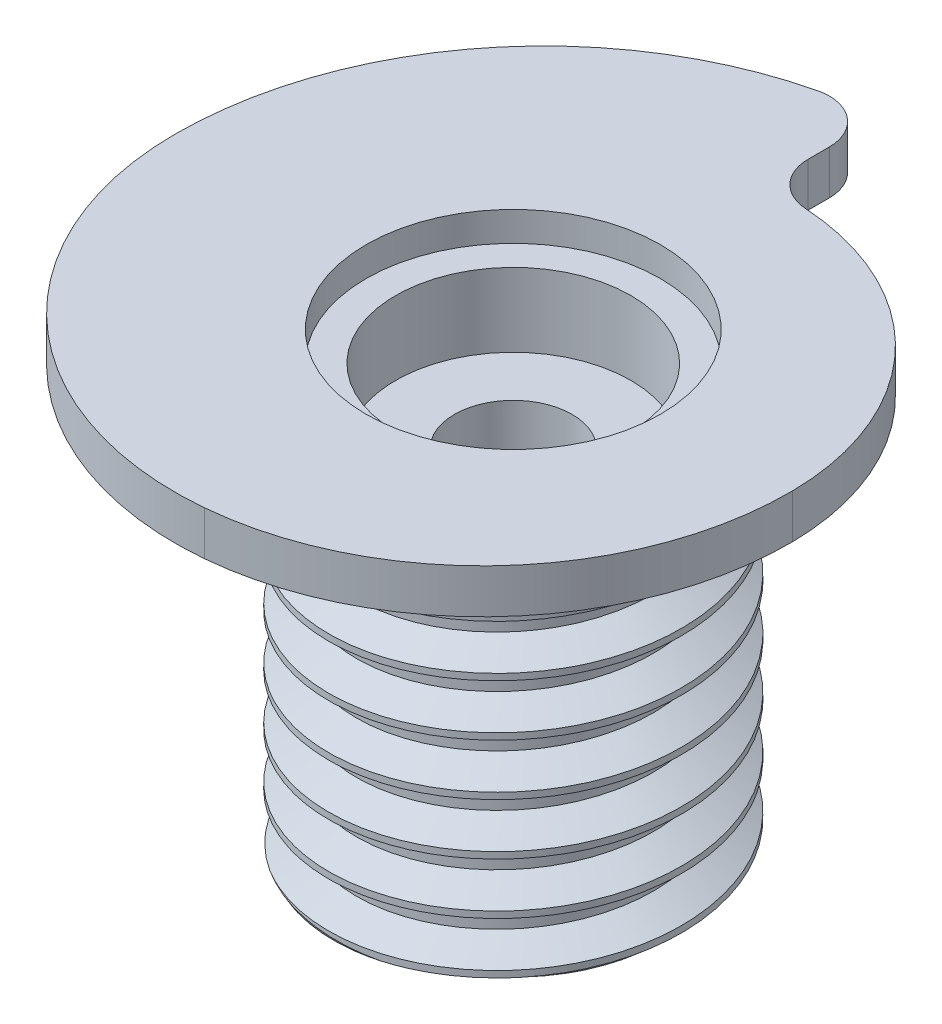
SolidWorks part; units mm, degrees
ref_plane "Front Plane" through (0, 0, 0) normal (0, 0, 1) x (1, 0, 0)
ref_plane "Top Plane" through (0, 0, 0) normal (0, 1, 0) x (1, 0, 0)
ref_plane "Right Plane" through (0, 0, 0) normal (1, 0, 0) x (0, 0, -1)
sketch "Sketch1" plane through (0, 0, 0) normal (1, 0, 0) x (0, 0, -1)
  line L4 (12, 28) -> (12, 0)
  line L6 (0, 0) -> (0, 28) construction
  line L7 (12, 28) -> (4, 28)
  line L10 (4, 28) -> (4, 5)
  line L11 (4, 5) -> (8, 5)
  line L12 (8, 5) -> (8, 0)
  line L13 (8, 0) -> (12, 0)
  dimension "D1" = 8
  dimension "D2" = 8
  dimension "D3" = 5
  dimension "D6" = 28
  dimension "D7" = 12
revolve "Revolve1" add sketch "Sketch1" angle 360 about L6
chamfer "Chamfer1" distance 1 angle 30 1 edges at (0, 0, -12) first distance on face at (0, 28, -12)
thread "Thread1" pitch 3.5 method cut profile "Thread Profile1" start angle 0, offset 0, length 48, pitch 3.5, diameter 24
ref_plane "Plane1" through (-12, 28, 0) normal (0, 0, 1) x (-1, 0, 0)
sketch "Thread Profile1" plane through (-12, 28, 0) normal (0, 0, 1) x (-1, 0, 0)
  line L0 (0, 0) -> (0, 3.5) construction
  line L11 (0, 0) -> (0, 3.0625)
  line L12 (0, 3.0625) -> (-1.8944, 1.9687)
  line L13 (-1.8944, 1.9687) -> (-1.8944, 1.0937)
  line L15 (-1.8944, 1.0937) -> (0, 0)
  line L17 (-1.8944, 1.5312) -> (0, 1.5312) construction
  point P2 (0, 0)
  dimension "Pitch" = 3.5
  dimension "Profile_Angle" = 60
  dimension "Profile_Land" = 0.875
  dimension "Profile_Height" = 1.8944
sketch "Sketch2" plane through (0, 28, 0) normal (0, 1, 0) x (1, 0, 0)
  line L1 (0, 11.547) -> (-10, -5.7735) construction
  line L2 (-10, -5.7735) -> (10, -5.7735) construction
  line L3 (10, -5.7735) -> (0, 11.547) construction
  circle A0 centre (0, 0) radius 5.7735 construction
  circle A1 centre (0, 11.547) radius 1.5
  circle A2 centre (10, -5.7735) radius 1.5
  circle A3 centre (-10, -5.7735) radius 1.5
  dimension "D2" = 3
  dimension "D1" = 20
extrude "Cut-Extrude1" [suppressed] cut sketch "Sketch2" against normal blind 4
sketch "Sketch3" plane through (0, 28, 0) normal (0, 1, 0) x (1, 0, 0)
  line L0 (0, 25) -> (0, -25) construction
  line L1 (-25, 0) -> (25, 0) construction
  line L2 (0, 25) -> (0, 17)
  circle A1 centre (0, 0) radius 17 construction
  circle A2 centre (0, 0) radius 19 construction
  circle A3 centre (0, 0) radius 21 construction
  circle A4 centre (0, 0) radius 23 construction
  circle A5 centre (0, 0) radius 25 construction
  arc A6 (0, 25) -> (-23, 0) centre (2.087, 0) ccw
  arc A7 (-23, 0) -> (0, -21) centre (-1.913, 0) ccw
  arc A8 (0, -21) -> (19, 0) centre (-1.8958, -0.1895) ccw
  arc A9 (19, 0) -> (0, 17) centre (1.7548, -0.1564) ccw
  dimension "D1" = 34
  dimension "D2" = 2
  dimension "D3" = 2
  dimension "D4" = 2
  dimension "D5" = 2
extrude "Boss-Extrude1" add sketch "Sketch3" along normal blind 3
sketch "Sketch6" plane through (0, 31, 0) normal (0, 1, 0) x (1, 0, 0)
  circle A0 centre (0, 0) radius 10
  dimension "D1" = 20
extrude "Cut-Extrude3" cut sketch "Sketch6" against normal blind 2
sketch "Sketch4" plane through (0, 29, 0) normal (0, 1, 0) x (1, 0, 0)
  circle A2 centre (0, 0) radius 8
  dimension "D1" = 16
extrude "Cut-Extrude2" cut sketch "Sketch4" against normal blind 5
fillet "Fillet1" radius 3 2 edges at (0, 29.5, -17) (0, 29.5, -25)
sketch "Sketch5" plane through (0, 31, 0) normal (0, 1, 0) x (1, 0, 0)
  arc A0 (-6.606, 16.744) -> (-18, 0) centre (0, 0) ccw construction
  arc A1 (-7.5235, 19.0695) -> (-20.5, 0) centre (0, 0) ccw
  arc A2 (-5.6885, 14.4184) -> (-15.5, 0) centre (0, 0) ccw
  arc A3 (-5.6885, 14.4184) -> (-7.5235, 19.0695) centre (-6.606, 16.744) ccw
  arc A4 (-20.5, 0) -> (-15.5, 0) centre (-18, 0) ccw
  arc A5 (-8.6169, -12.278) -> (8.6169, -12.278) centre (0, 0) ccw construction
  arc A6 (-9.7658, -13.9151) -> (9.7658, -13.9151) centre (0, 0) ccw
  arc A7 (-7.4679, -10.6409) -> (7.4679, -10.6409) centre (0, 0) ccw
  arc A8 (-7.4679, -10.6409) -> (-9.7658, -13.9151) centre (-8.6169, -12.278) ccw
  arc A9 (9.7658, -13.9151) -> (7.4679, -10.6409) centre (8.6169, -12.278) ccw
  arc A10 (13.9041, 1.6355) -> (6.0016, 12.6484) centre (0, 0) ccw construction
  arc A11 (15.3939, 1.8107) -> (6.6446, 14.0035) centre (0, 0) ccw
  arc A12 (12.4144, 1.4603) -> (5.3586, 11.2932) centre (0, 0) ccw
  arc A13 (12.4144, 1.4603) -> (15.3939, 1.8107) centre (13.9041, 1.6355) ccw
  arc A14 (6.6446, 14.0035) -> (5.3586, 11.2932) centre (6.0016, 12.6484) ccw
  point P4 (-14.8813, 10.1265)
  point P9 (0, -15)
  point P18 (11.3745, 8.1621)
  dimension "D1" = 18
  dimension "D2" = 2.5
  dimension "D3" = 15
  dimension "D4" = 2
  dimension "D5" = 14
  dimension "D6" = 1.5
